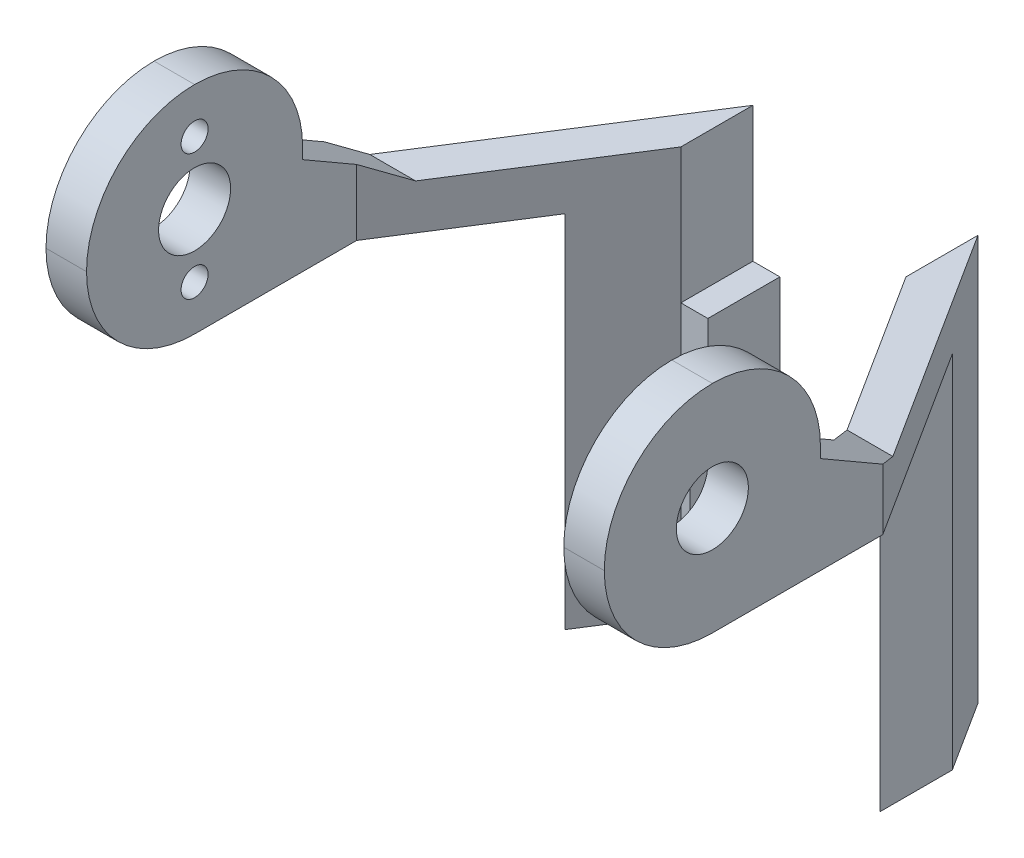
SolidWorks part; units mm, degrees
ref_plane "前视基准面" through (0, 0, 0) normal (0, 0, 1) x (1, 0, 0)
ref_plane "上视基准面" through (0, 0, 0) normal (0, 1, 0) x (1, 0, 0)
ref_plane "右视基准面" through (0, 0, 0) normal (1, 0, 0) x (0, 0, -1)
sketch "Sketch1" plane through (0, 0, 0) normal (0, 1, 0) x (1, 0, 0)
  line L0 (-31, 15.9286) -> (-31, -15)
  line L1 (-31, -15) -> (-26.5, -15)
  line L2 (-26.5, -15) -> (-26.5, 15)
  line L3 (-26.5, 15) -> (26.5, -15) construction
  line L4 (26.5, -15) -> (26.5, 15)
  line L5 (26.5, 15) -> (-26.5, -15) construction
  line L6 (26.5, -15) -> (31, -15)
  line L7 (31, -15) -> (31, 15.9286)
  line L8 (-31, 15.9286) -> (-12.5, 45)
  line L9 (-12.5, 45) -> (12.5, 45)
  line L10 (12.5, 45) -> (31, 15.9286)
  line L11 (-26.5, 15) -> (-12.5, 37)
  line L12 (-12.5, 37) -> (12.5, 37)
  line L13 (12.5, 37) -> (26.5, 15)
  line L14 (0, 45) -> (0, 37) construction
  line L15 (-26.5, -15) -> (26.5, -15) construction
  line L16 (0, 37) -> (0, 0) construction
  dimension "D4" = 8
  dimension "D1" = 53
  dimension "D2" = 30
  dimension "D3" = 4.5
  dimension "D6" = 25
  dimension "D7" = 60
extrude "Boss-Extrude1" add sketch "Sketch1" along normal blind 5
sketch "Sketch2" plane through (0, 5, 0) normal (0, 1, 0) x (1, 0, 0)
  line L0 (-31, 15.9286) -> (-31, -15) construction
  line L1 (-26.5, -15) -> (-26.5, 15) construction
  line L3 (-31, -15) -> (-26.5, -15) construction
  line L4 (-31, 9) -> (-31, -15)
  line L5 (-26.5, -15) -> (-26.5, 9)
  line L6 (-26.5, 9) -> (-31, 9)
  line L7 (-31, -15) -> (-26.5, -15)
  line L8 (26.5, 9) -> (31, 9)
  line L13 (26.5, 15) -> (26.5, -15) construction
  line L14 (31, -15) -> (31, 15.9286) construction
  line L15 (26.5, -15) -> (31, -15) construction
  line L18 (26.5, 9) -> (26.5, -15)
  line L19 (31, -15) -> (31, 9)
  line L20 (26.5, -15) -> (31, -15)
  dimension "D1" = 24
extrude "Boss-Extrude2" add sketch "Sketch2" along normal blind 19
sketch "Sketch5" plane through (0, 5, 0) normal (0, 1, 0) x (1, 0, 0)
  line L0 (12.5, 45) -> (-12.5, 45) construction
  line L1 (0, 45) -> (0, 37) construction
  line L2 (-12.5, 37) -> (12.5, 37) construction
  circle A0 centre (0, 41) radius 1.7
  point P0 (0, 45)
  dimension "D1" = 4
  dimension "D2" = 3.4
extrude "Cut-Extrude1" cut sketch "Sketch5" against normal up to next
sketch "Sketch6" plane through (0, 0, -45) normal (0, 0, -1) x (-1, 0, 0)
  line L0 (-12.5, 5) -> (12.5, 5) construction
  line L1 (-7, 2) -> (7, 2)
  line L2 (-7, 2) -> (-7, 5)
  line L3 (-7, 5) -> (7, 5)
  line L4 (7, 2) -> (7, 5)
  line L5 (-7, 2) -> (7, 5) construction
  line L6 (-7, 5) -> (7, 2) construction
  line L7 (0, 0) -> (0, 3.5) construction
  point P0 (0, 3.5)
  dimension "D1" = 3
  dimension "D2" = 14
extrude "Cut-Extrude2" cut sketch "Sketch6" against normal up to surface (8 mm away) up to face at (0, 2.5, -37)
sketch "Sketch7" plane through (-26.5, 0, 0) normal (1, 0, 0) x (0, 0, -1)
  line L0 (-3, 12) -> (-3, 24) construction
  line L1 (-15, 24) -> (9, 24) construction
  line L2 (-3, 12) -> (-15, 12) construction
  line L3 (-15, 24) -> (-15, 0) construction
  circle B0 centre (-3, 19) radius 1.5
  circle B1 centre (-3, 5) radius 1.5
sketch_block_instance "ArmHoles-1"
sketch_block "ArmHoles" parameters "D1"=4.0842
extrude "Cut-Extrude3" cut sketch "Sketch7" against normal up to next
sketch "Sketch8" plane through (-26.5, 0, 0) normal (1, 0, 0) x (0, 0, -1)
  line L0 (-3, 19) -> (-3, 5) construction
  circle A0 centre (-3, 12) radius 4
  dimension "D1" = 8
extrude "Cut-Extrude4" cut sketch "Sketch8" against normal through all both and the other way through all
fillet "Fillet1" radius 12 6 edges at (28.75, 0, 15) (-28.75, 0, 15) (-28.75, 24, -9) (28.75, 24, -9) (28.75, 24, 15) (-28.75, 24, 15)
chamfer "Chamfer2" distance 10 angle 30 2 edges at (28.75, 5, -9) first distance on face at (-18.9688, 5, -26.6741) first distance on face at (19.25, 5, -26.6161)
sketch "Sketch10" plane through (0, 5, 0) normal (0, 1, 0) x (1, 0, 0)
  line L0 (-7, 41) -> (-10, 41) construction
  line L1 (-7, 37) -> (-7, 45) construction
  circle A0 centre (-10, 41) radius 1.7
  dimension "D1" = 3.4
  dimension "D2" = 3
extrude "Cut-Extrude5" cut sketch "Sketch10" against normal up to next
mirror "Mirror1" about plane through (0, 0, 0) normal (1, 0, 0) of "Cut-Extrude5"
sketch "草图1" plane through (0, 0, 0) normal (0, -1, 0) x (1, 0, 0)
  line L0 (0, -37) -> (0, -45) construction
  line L1 (-12.5, -37) -> (12.5, -37) construction
  line L2 (12.5, -45) -> (-12.5, -45) construction
  line L4 (-12.5, -37) -> (12.5, -37)
  line L5 (-12.5, -37) -> (-12.5, -45)
  line L6 (-12.5, -45) -> (12.5, -45)
  line L7 (12.5, -37) -> (12.5, -45)
  dimension "D1" = 25
extrude "切除-拉伸1" cut sketch "草图1" against normal through all
sketch "草图2" plane through (0, 0, 0) normal (0, -1, 0) x (-1, 0, 0)
  line L0 (17.5, 29.1429) -> (17.5, 37.1429)
  line L1 (26.5, 15) -> (12.5, 37) construction
  line L2 (12.5, 45) -> (31, 15.9286) construction
  line L3 (12.5, 37) -> (12.5, 45) construction
  line L4 (0, 0) -> (0, 49.8816) construction
  line L5 (-17.5, 29.1429) -> (-17.5, 37.1429)
  line L6 (-17.5, 37.1429) -> (-12.5, 45)
  line L7 (-12.5, 45) -> (-12.5, 37)
  line L8 (-12.5, 37) -> (-17.5, 29.1429)
  line L9 (12.5, 37) -> (17.5, 29.1429)
  line L10 (17.5, 37.1429) -> (12.5, 45)
  line L11 (12.5, 45) -> (12.5, 37)
  line L12 (17.5, 29.1429) -> (17.5, 37.1429)
  line M1 (12.5, 45) -> (12.5, 37)
  line M2 (12.5, 37) -> (26.5, 15)
  line M6 (31, 15.9286) -> (12.5, 45)
  dimension "D1" = 5
extrude "凸台-拉伸2" add sketch "草图2" along normal blind 40 contours L8 L7 L6 L5 | L0 M2 M6 M1 region at (-15, 0, -37.0714) region at (15, 0, -37.0714)
sketch "草图4" plane through (12.5, 0, 0) normal (-1, 0, 0) x (0, 0, 1)
  line L5 (-45, -20) -> (-45, -10)
  line L6 (-45, -10) -> (-37, -10)
  line L7 (-37, -20) -> (-37, -10)
  line L8 (-45, -20) -> (-37, -20)
sketch "草图5" plane through (-12.5, 0, 0) normal (1, 0, 0) x (0, 0, -1)
  line L5 (45, -20) -> (37, -20)
  line L6 (37, -20) -> (37, -10)
  line L7 (45, -20) -> (45, -10)
  line L8 (45, -10) -> (37, -10)
extrude "凸台-拉伸3" add sketch "草图5" along normal blind 3
extrude "凸台-拉伸4" add sketch "草图4" along normal blind 3
sketch "草图7" plane through (12.5, 0, 0) normal (-1, 0, 0) x (0, 0, 1)
  line L0 (-37, -20) -> (-37, -40) construction
  line L1 (-37, -26.5) -> (-45, -26.5)
  line L2 (-37, -26.5) -> (-37, -38.5)
  line L3 (-37, -38.5) -> (-45, -38.5)
  line L4 (-45, -26.5) -> (-45, -38.5)
  line L5 (-45, -20) -> (-45, -40) construction
  line L6 (-45, -20) -> (-37, -20) construction
  dimension "D1" = 12
  dimension "D2" = 6.5
extrude "凸台-拉伸5" add sketch "草图7" along normal blind 1
mirror "镜向1" about plane through (0, 0, 0) normal (1, 0, 0) of "凸台-拉伸5"
